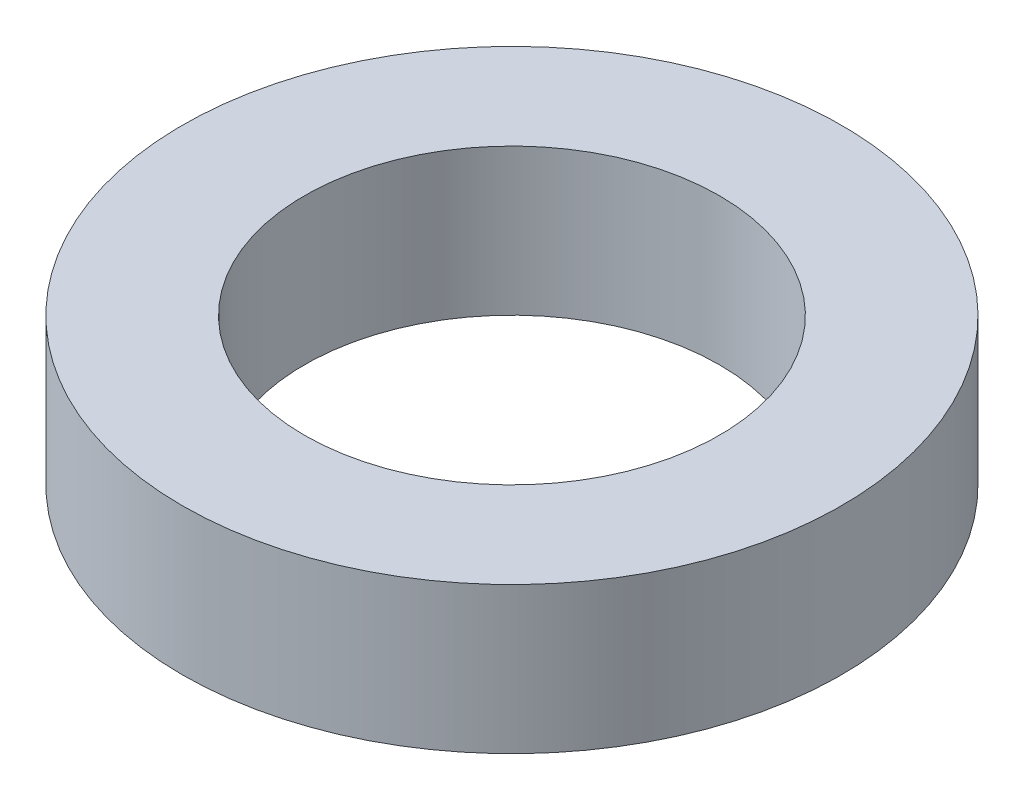
SolidWorks part; units mm, degrees
ref_plane "Front Plane" through (0, 0, 0) normal (0, 0, 1) x (1, 0, 0)
ref_plane "Top Plane" through (0, 0, 0) normal (0, 1, 0) x (1, 0, 0)
ref_plane "Right Plane" through (0, 0, 0) normal (1, 0, 0) x (0, 0, -1)
sketch "Sketch1" plane through (0, 0, 0) normal (0, 1, 0) x (1, 0, 0)
  circle A0 centre (0, 0) radius 67.5
  dimension "FLANGE_OD" = 135
extrude "Boss-Extrude1" add sketch "Sketch1" along normal blind 30
sketch "Sketch2" plane through (0, 0, 0) normal (0, 1, 0) x (1, 0, 0)
  circle A0 centre (0, 0) radius 42.5
  dimension "BORE_D" = 85
extrude "Cut-Extrude1" cut sketch "Sketch2" along normal through all
sketch "Sketch3" plane through (0, 30, 0) normal (0, 1, 0) x (1, 0, 0)
  circle A0 centre (0, 0) radius 24.2415 construction
  circle A1 centre (-24.2415, 0) radius 2.8875
  dimension "BOLT_D" = 5.775
  dimension "BOLT_PCD" = 48.4831
extrude "Cut-Extrude2" cut sketch "Sketch3" against normal blind 28.57 rebuild error yes
pattern_circular "CirPattern1" count 5 over 360 rebuild error yes
